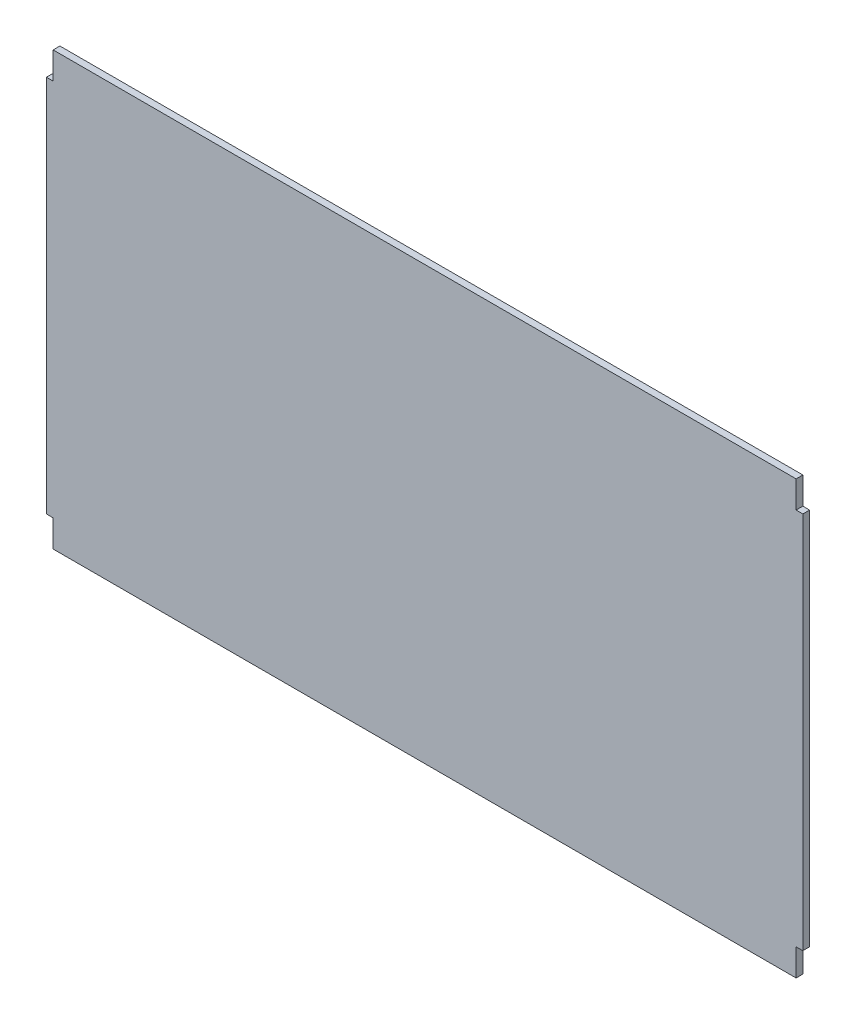
SolidWorks part; units mm, degrees
ref_plane "Front Plane" through (0, 0, 0) normal (0, 0, 1) x (1, 0, 0)
ref_plane "Top Plane" through (0, 0, 0) normal (0, 1, 0) x (1, 0, 0)
ref_plane "Right Plane" through (0, 0, 0) normal (1, 0, 0) x (0, 0, -1)
sketch "Sketch1" plane through (0, 0, 0) normal (0, 0, 1) x (1, 0, 0)
  line L0 (3.175, 203.2) -> (3.175, 190.5)
  line L1 (3.175, 0) -> (352.425, 0)
  line L2 (0, 12.7) -> (0, 190.5)
  line L3 (3.175, 203.2) -> (352.425, 203.2)
  line L4 (355.6, 12.7) -> (355.6, 190.5)
  line L5 (3.175, 190.5) -> (0, 190.5)
  line L6 (3.175, 12.7) -> (0, 12.7)
  line L7 (3.175, 12.7) -> (3.175, 0)
  line L8 (352.425, 0) -> (352.425, 12.7)
  line L9 (352.425, 12.7) -> (355.6, 12.7)
  line L10 (352.425, 203.2) -> (352.425, 190.5)
  line L11 (352.425, 190.5) -> (355.6, 190.5)
  dimension "D1" = 355.6
  dimension "D3" = 12.7
  dimension "D4" = 12.7
  dimension "D5" = 12.7
  dimension "D6" = 12.7
  dimension "D7" = 3.175
  dimension "D8" = 3.175
  dimension "D9" = 3.175
extrude "Boss-Extrude1" add sketch "Sketch1" along normal blind 3.175
